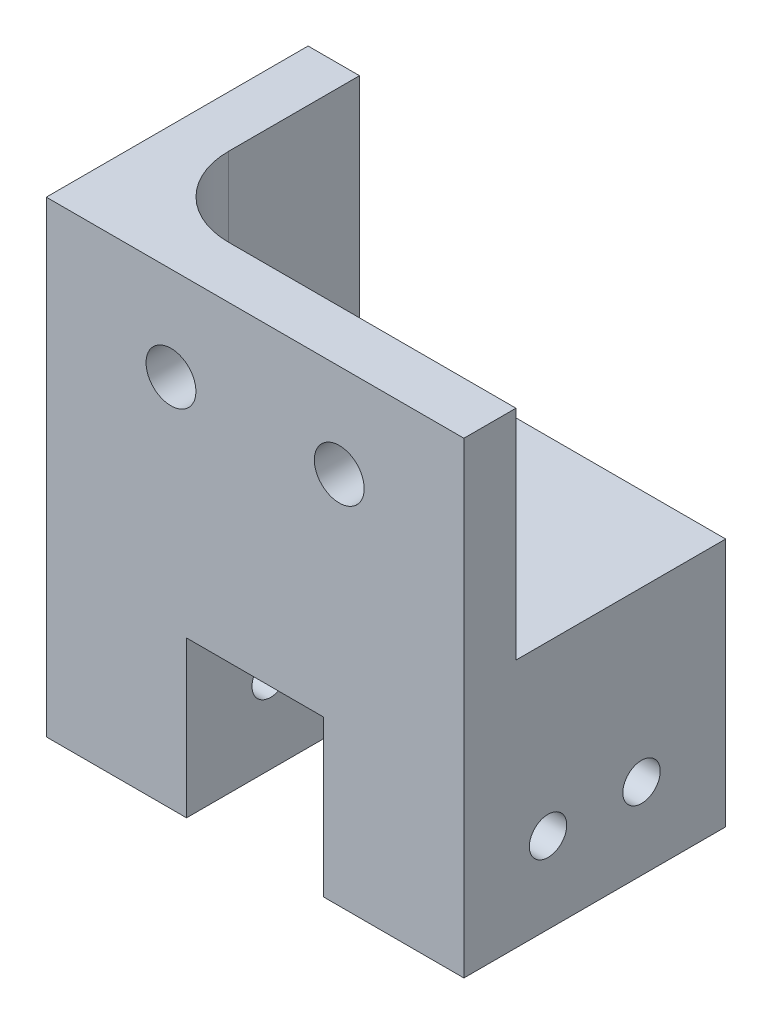
SolidWorks part; units mm, degrees
material "6061 Legierung"
ref_plane "Ebene vorne" through (0, 0, 0) normal (0, 0, 1) x (1, 0, 0)
ref_plane "Ebene oben" through (0, 0, 0) normal (0, 1, 0) x (1, 0, 0)
ref_plane "Ebene rechts" through (0, 0, 0) normal (1, 0, 0) x (0, 0, -1)
sketch "Skizze1" plane through (0, 0, 0) normal (0, 0, 1) x (1, 0, 0)
  line L13 (-11, 155) -> (11, 155)
  line L15 (11, 155) -> (11, 130)
  line L17 (11, 130) -> (33.5, 130)
  line L18 (33.5, 130) -> (33.5, 205)
  line L19 (33.5, 205) -> (-33.5, 205)
  line L23 (-33.5, 130) -> (-33.5, 205)
  line L24 (-11, 130) -> (-33.5, 130)
  line L25 (-11, 155) -> (-11, 130)
  point P16 (0, 205)
  point P19 (0, 155)
sketch "Skizze3" plane through (0, 0, 0) normal (0, 0, 1) x (1, 0, 0)
  line L9 (0, 205) -> (33.5, 205)
  line L10 (33.5, 205) -> (33.5, 130)
  line L11 (33.5, 130) -> (11, 130)
  line L12 (11, 130) -> (11, 155)
  line L13 (11, 155) -> (0, 155)
  line L14 (0, 205) -> (-33.5, 205)
  line L15 (-33.5, 205) -> (-33.5, 130)
  line L16 (-33.5, 130) -> (-11, 130)
  line L17 (-11, 130) -> (-11, 155)
  line L18 (-11, 155) -> (0, 155)
sketch "Skizze4" plane through (0, 0, 0) normal (1, 0, 0) x (0, 0, -1)
  line L0 (15, 0) -> (-15, 0)
  point P8 (0, 0)
extrude "Aufsatz-Linear austragen1" add sketch "Skizze3" along normal blind 21 and the other way blind 21
sketch "Skizze5" plane through (0, 0, 0) normal (0, 1, 0) x (1, 0, 0)
  line L1 (-12.6, 12.65) -> (25.15, 12.65)
  line L2 (25.15, 12.65) -> (25.15, -12.65)
  line L3 (25.15, -12.65) -> (-12.6, -12.65)
  line L5 (-12.6, 10.85) -> (23.35, 10.85)
  line L6 (23.35, 10.85) -> (23.35, -10.85)
  line L7 (23.35, -10.85) -> (-12.6, -10.85)
  arc A0 (-12.6, 12.65) -> (-12.6, -12.65) centre (-12.6, 0) ccw
  arc A1 (-12.6, 10.85) -> (-12.6, -10.85) centre (-12.6, 0) ccw
sketch "Skizze6" plane through (0, 205, 0) normal (0, 1, 0) x (1, 0, 0)
  line L0 (-25.25, 0) -> (-25.25, 21)
  line L1 (33.5, 21) -> (-33.5, 21) construction
  line L2 (-25.25, 21) -> (33.5, 21)
  line L3 (33.5, 21) -> (33.5, -21) construction
  line L4 (33.5, 21) -> (33.5, -12.65)
  line L5 (33.5, -12.65) -> (-12.6, -12.65)
  arc A0 (-12.6, 12.65) -> (-12.6, -12.65) centre (-12.6, 0) ccw construction
  arc A1 (-25.25, 0) -> (-12.6, -12.65) centre (-12.6, 0) ccw
sketch "StingHeigtPos" plane through (0, 0, 0) normal (0, 0, 1) x (1, 0, 0)
  line L0 (0, 170) -> (0, 630)
extrude "Schnitt-Linear austragen1" cut sketch "Skizze6" against normal up to vertex (35 mm away) up to point (0, 170, 0)
sketch "Holes" plane through (0, 0, 0) normal (0, 0, 1) x (1, 0, 0)
  circle A0 centre (13.5, 190) radius 4
  circle A1 centre (-13.5, 190) radius 4
sketch "Skizze9" plane through (0, 0, 0) normal (0, 0, 1) x (1, 0, 0)
  circle A0 centre (-13.5, 190) radius 4
  circle A1 centre (13.5, 190) radius 4
extrude "Schnitt-Linear austragen2" cut sketch "Skizze9" along normal up to surface (21 mm away) up to face at (0, 155, 21)
sketch "Skizze10" plane through (0, 0, 0) normal (1, 0, 0) x (0, 0, -1)
  line L2 (0, 90) -> (21.451, 90) construction
  circle A0 centre (7.5, 37) radius 3
  circle A1 centre (-7.5, 37) radius 3
  circle A4 centre (-7.5, 143) radius 3
  circle A5 centre (7.5, 143) radius 3
sketch "Skizze11" plane through (0, 0, 0) normal (1, 0, 0) x (0, 0, -1)
  circle A0 centre (7.5, 143) radius 3
  circle A1 centre (-7.5, 143) radius 3
extrude "Schnitt-Linear austragen3" cut sketch "Skizze11" against normal up to surface and the other way up to surface up to face at (-33.5, 167.5, 0) other way up to face at (33.5, 168.3333, 4.2167)
